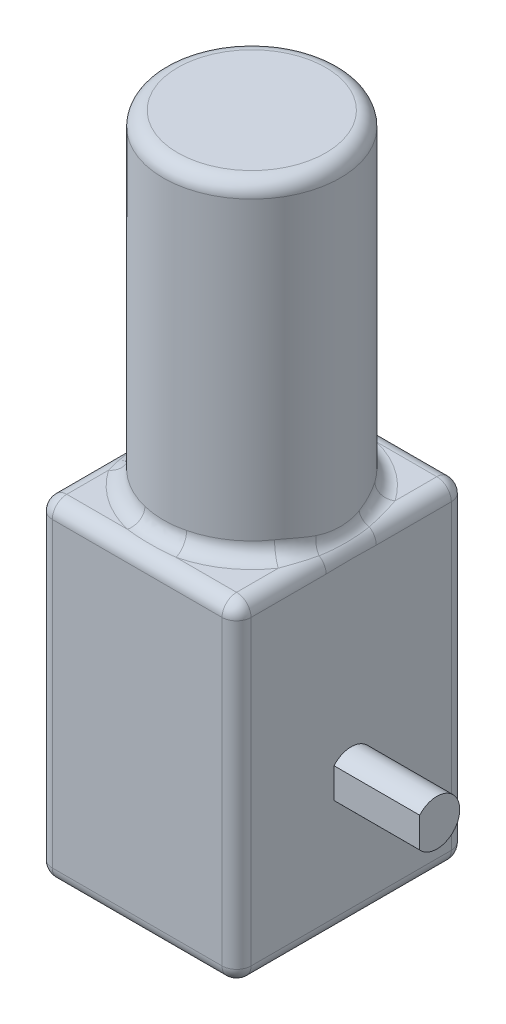
SolidWorks part; units mm, degrees
ref_plane "Front Plane" through (0, 0, 0) normal (0, 0, 1) x (1, 0, 0)
ref_plane "Top Plane" through (0, 0, 0) normal (0, 1, 0) x (1, 0, 0)
ref_plane "Right Plane" through (0, 0, 0) normal (1, 0, 0) x (0, 0, -1)
sketch "Sketch2" plane through (0, 0, 0) normal (0, 1, 0) x (1, 0, 0)
  circle A0 centre (0, 0) radius 15.494
  dimension "D1" = 30.988
extrude "Boss-Extrude1" add sketch "Sketch2" along normal blind 56.896
sketch "Sketch3" plane through (0, 0, 0) normal (0, -1, 0) x (1, 0, 0)
  line L1 (-17.399, 20.066) -> (17.399, 20.066)
  line L2 (-17.399, 20.066) -> (-17.399, -20.066)
  line L3 (-17.399, -20.066) -> (17.399, -20.066)
  line L4 (17.399, 20.066) -> (17.399, -20.066)
  line L5 (-17.399, 20.066) -> (17.399, -20.066) construction
  line L6 (-17.399, -20.066) -> (17.399, 20.066) construction
  point P0 (0, 0)
  dimension "D1" = 40.132
  dimension "D2" = 34.798
extrude "Boss-Extrude2" add sketch "Sketch3" along normal blind 57.912
sketch "Sketch4" plane through (17.399, 0, 0) normal (1, 0, 0) x (0, 0, -1)
  line L0 (20.066, -57.912) -> (-20.066, -57.912) construction
  line L5 (-4, -34.912) -> (-3.0094, -34.912)
  line L6 (-3.0094, -32.2769) -> (-3.0094, -37.5471)
  circle A1 centre (0, -34.912) radius 4
  dimension "D3" = 0.9906
  dimension "D1" = 8
  dimension "D2" = 23
extrude "Boss-Extrude3" add sketch "Sketch4" along normal blind 15 contours L6 A1 region at (17.399, -34.912, -0.2613)
fillet "Fillet1" radius 2.54 12 edges at (-17.399, 0, 0) (17.399, -28.956, 20.066) (-17.399, -28.956, 20.066) (0, 0, 20.066) (-17.399, -28.956, -20.066) (17.399, -28.956, -20.066) (0, 0, -20.066) (0, -57.912, -20.066) (-17.399, -57.912, 0) (0, -57.912, 20.066) (17.399, -57.912, 0) (17.399, 0, 0)
fillet "Fillet2" radius 2.54 5 edges at (15.494, 0, 0) (0, 0, 15.494) (-15.494, 0, 0) (0, 0, -15.494) (0, 56.896, 15.494)
